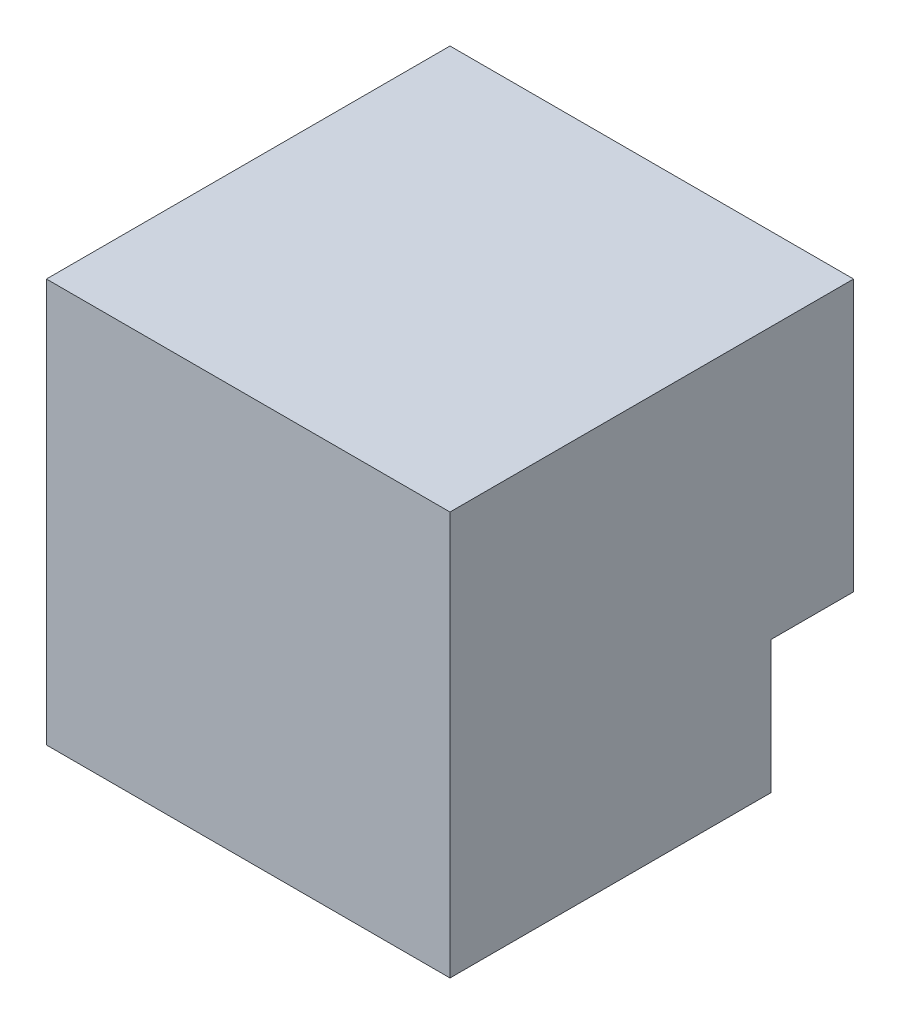
SolidWorks part; units mm, degrees
ref_plane "Front Plane" through (0, 0, 0) normal (0, 0, 1) x (1, 0, 0)
ref_plane "Top Plane" through (0, 0, 0) normal (0, 1, 0) x (1, 0, 0)
ref_plane "Right Plane" through (0, 0, 0) normal (1, 0, 0) x (0, 0, -1)
sketch "Sketch1" plane through (0, 0, 0) normal (0, 0, 1) x (1, 0, 0)
  line L1 (0, 0) -> (50.8, 0)
  line L2 (0, 0) -> (0, 50.8)
  line L3 (0, 50.8) -> (50.8, 50.8)
  line L4 (50.8, 0) -> (50.8, 50.8)
  dimension "D1" = 50.8
  dimension "D2" = 50.8
extrude "Boss-Extrude1" add sketch "Sketch1" along normal blind 50.8
sketch "Sketch5" plane through (0, 0, 0) normal (0, 0, -1) x (-1, 0, 0)
  line L0 (-50.8, 0) -> (-50.8, 50.8) construction
  line L1 (0, 0) -> (-50.8, 0)
  line L2 (0, 0) -> (0, 16.695)
  line L3 (0, 16.695) -> (-50.8, 16.695)
  line L4 (-50.8, 0) -> (-50.8, 16.695)
extrude "Cut-Extrude1" cut sketch "Sketch5" against normal blind 10.414
